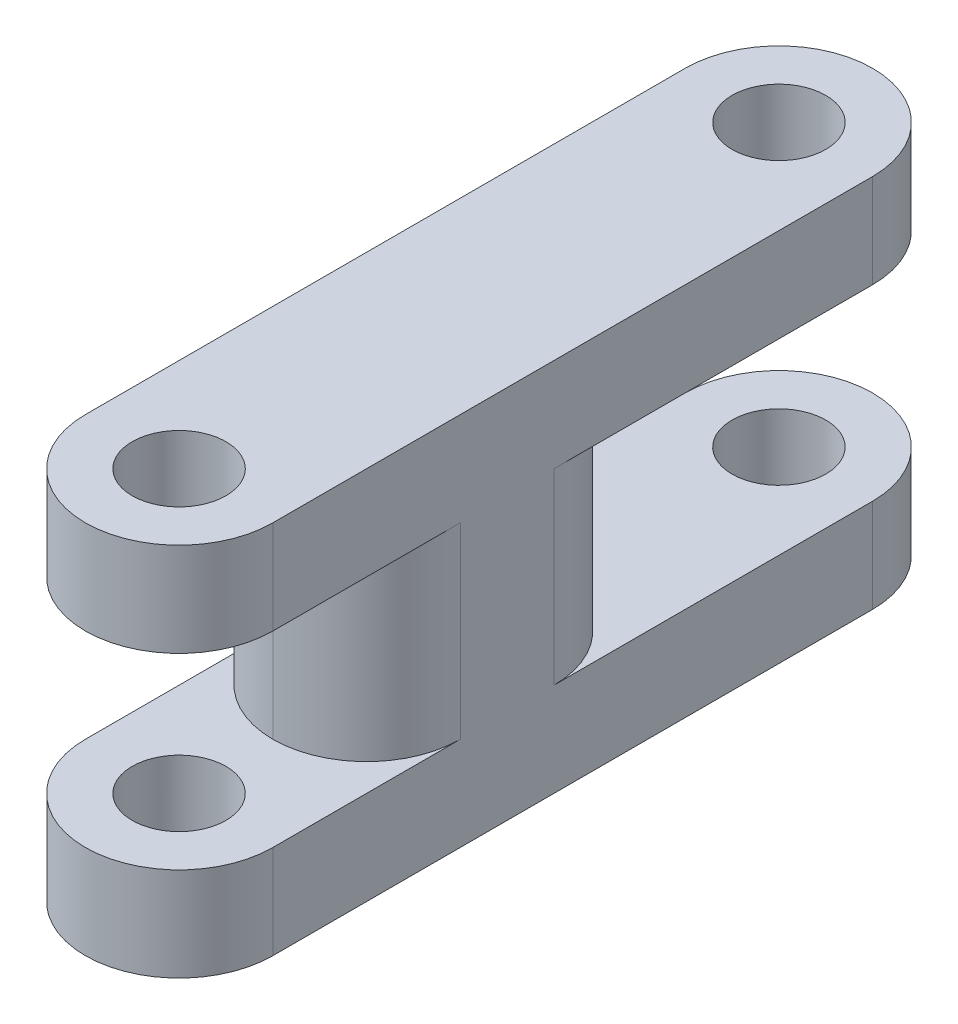
SolidWorks part; units mm, degrees
ref_plane "Front Plane" through (0, 0, 0) normal (0, 0, 1) x (1, 0, 0)
ref_plane "Top Plane" through (0, 0, 0) normal (0, 1, 0) x (1, 0, 0)
ref_plane "Right Plane" through (0, 0, 0) normal (1, 0, 0) x (0, 0, -1)
sketch "Sketch1" plane through (0, 0, 0) normal (0, 1, 0) x (1, 0, 0)
  line L0 (0, 0) -> (0, 32) construction
  line L1 (-5, 0) -> (-5, 32)
  line L2 (5, 0) -> (5, 32)
  arc A0 (-5, 0) -> (5, 0) centre (0, 0) ccw
  arc A1 (5, 32) -> (-5, 32) centre (0, 32) ccw
  circle A2 centre (0, 32) radius 2.5
  circle A3 centre (0, 0) radius 2.5
  point P3 (0, 16)
  dimension "D1" = 5
  dimension "D3" = 5
  dimension "D4" = 5
  dimension "D2" = 32
extrude "Boss-Extrude1" add sketch "Sketch1" along normal blind 20
sketch "Sketch2" plane through (5, 0, 0) normal (1, 0, 0) x (0, 0, -1)
  line L0 (0, 20) -> (32, 20) construction
  line L1 (-5, 15) -> (5, 15)
  line L2 (-5, 15) -> (-5, 5)
  line L3 (-5, 5) -> (5, 5)
  line L4 (5, 15) -> (5, 5)
  line L5 (0, 20) -> (0, 0) construction
  dimension "D1" = 10
  dimension "D2" = 10
  dimension "D3" = 5
  dimension "D4" = 5
extrude "Cut-Extrude1" cut sketch "Sketch2" against normal blind 15
ref_plane "Plane1" through (0, 0, -15) normal (0, 0, 1) x (1, 0, 0)
mirror "Mirror1" about plane through (0, 0, -15) normal (0, 0, 1) of "Cut-Extrude1"
fillet "Fillet1" radius 5 4 edges at (-5, 10, -25) (5, 10, -25) (-5, 10, -5) (5, 10, -5)
sketch "Sketch3" plane through (5, 0, 0) normal (1, 0, 0) x (0, 0, -1)
  line L9 (20, 5) -> (45, 5)
  line L10 (20, 5) -> (20, 15)
  line L11 (20, 15) -> (45, 15)
  line L12 (45, 5) -> (45, 15)
  dimension "D1" = 10
  dimension "D2" = 25
extrude "Cut-Extrude3" cut sketch "Sketch3" against normal blind 10
fillet "Fillet3" radius 5 2 edges at (-5, 10, -20) (5, 10, -20)
